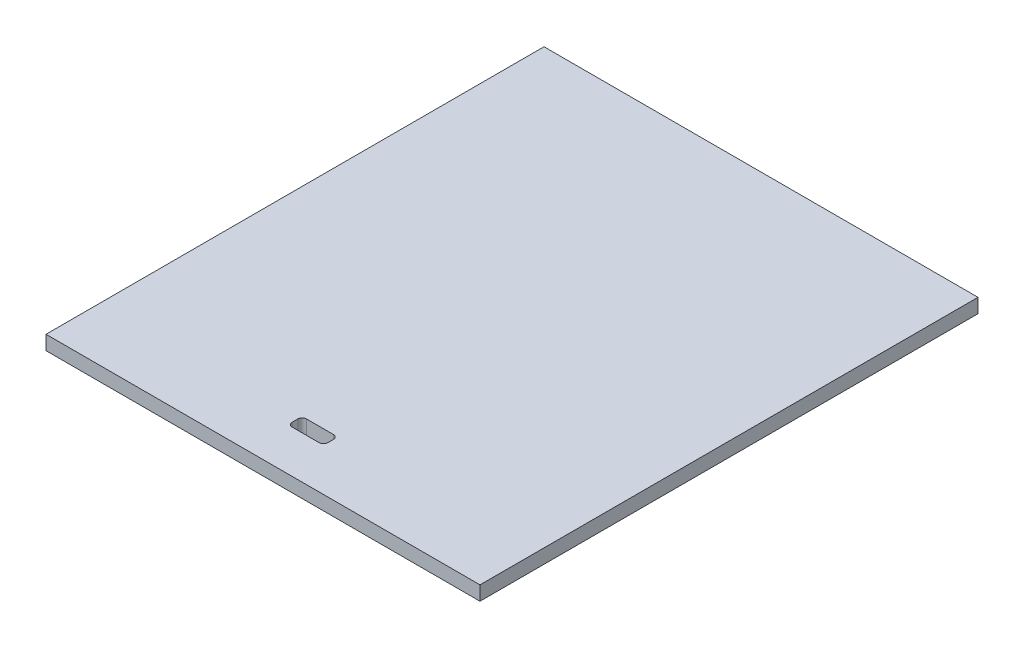
SolidWorks part; units mm, degrees
ref_plane "前视基准面" through (0, 0, 0) normal (0, 0, 1) x (1, 0, 0)
ref_plane "上视基准面" through (0, 0, 0) normal (0, 1, 0) x (1, 0, 0)
ref_plane "右视基准面" through (0, 0, 0) normal (1, 0, 0) x (0, 0, -1)
other "Configuration Table"
sketch "草图1" plane through (0, 0, 0) normal (0, 1, 0) x (1, 0, 0)
  line L0 (610, 0) -> (610, 230)
  line L1 (0, 0) -> (610, 0)
  line L2 (0, 0) -> (0, 700)
  line L3 (0, 700) -> (610, 700)
  line L4 (610, 230) -> (610, 700)
  dimension "D1" = 610
  dimension "D2" = 700
extrude "凸台-拉伸1" add sketch "草图1" along normal blind 20
sketch "草图2" plane through (0, 20, 0) normal (0, 1, 0) x (1, 0, 0)
  line L0 (0, 0) -> (610, 0) construction
  line L1 (286, 80) -> (324, 80)
  line L2 (280, 74) -> (280, 66)
  line L3 (286, 60) -> (324, 60)
  line L4 (330, 74) -> (330, 66)
  arc A0 (324, 80) -> (330, 74) centre (324, 74) cw
  arc A1 (324, 60) -> (330, 66) centre (324, 66) ccw
  arc A2 (280, 66) -> (286, 60) centre (286, 66) ccw
  arc A3 (286, 80) -> (280, 74) centre (286, 74) ccw
  point P4 (305, 80)
  point P7 (305, 0)
  point P10 (330, 80)
  point P13 (330, 60)
  point P16 (280, 60)
  dimension "D5" = 6
  dimension "D1" = 20
  dimension "D2" = 50
  dimension "D3" = 0
  dimension "D4" = 60
extrude "切除-拉伸1" cut sketch "草图2" against normal blind 20
